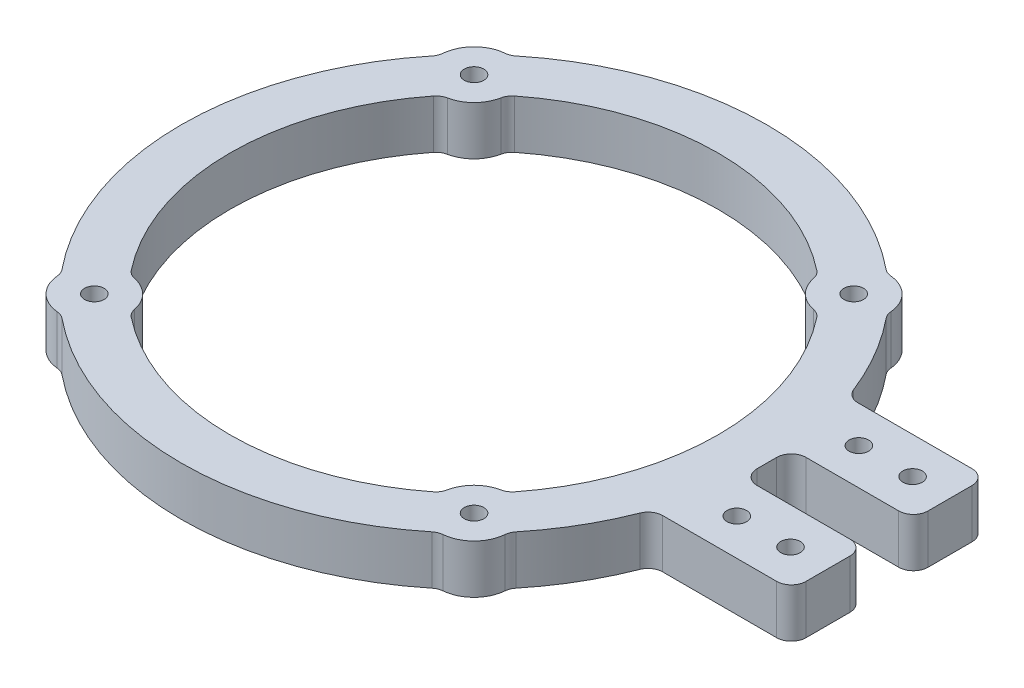
SolidWorks part; units mm, degrees
material "6063-T83"
ref_plane "Front Plane" through (0, 0, 0) normal (0, 0, 1) x (1, 0, 0)
ref_plane "Top Plane" through (0, 0, 0) normal (0, 1, 0) x (1, 0, 0)
ref_plane "Right Plane" through (0, 0, 0) normal (1, 0, 0) x (0, 0, -1)
sketch "Sketch1" plane through (0, 0, 0) normal (0, 1, 0) x (1, 0, 0)
  line L0 (0, -50) -> (0, -60) construction
  line L1 (0, 0) -> (0, -50) construction
  line L2 (56.5685, -20) -> (85, -20)
  line L3 (85, -20) -> (85, -5)
  line L4 (85, -5) -> (60, -5)
  line L5 (60, -5) -> (60, 5)
  line L6 (60, 5) -> (85, 5)
  line L7 (85, 5) -> (85, 20)
  line L8 (85, 20) -> (56.5685, 20)
  circle A0 centre (0, 0) radius 50
  circle A1 centre (0, 0) radius 60 construction
  arc A2 (56.5685, 20) -> (56.5685, -20) centre (0, 0) ccw
  dimension "D1" = 100
  dimension "D2" = 10
  dimension "D3" = 10
  dimension "D4" = 15
  dimension "D6" = 25
extrude "Boss-Extrude1" add sketch "Sketch1" along normal blind 10
sketch "Sketch3" plane through (0, 10, 0) normal (0, 1, 0) x (1, 0, 0)
  line L0 (38.8909, 38.8909) -> (38.8909, -38.8909) construction
  line L1 (60, -5) -> (60, 5) construction
  circle A0 centre (0, 0) radius 55 construction
  circle A1 centre (38.8909, -38.8909) radius 7
  circle A2 centre (-38.8909, -38.8909) radius 7
  circle A3 centre (-38.8909, 38.8909) radius 7
  circle A4 centre (38.8909, 38.8909) radius 7
  point P14 (0, 0)
  dimension "D1" = 110
  dimension "D2" = 14
  dimension "D3" = 4
extrude "Boss-Extrude2" add sketch "Sketch3" against normal up to surface (10 mm away) up to face at (57.0711, 0, 0)
sketch "Sketch4" plane through (0, 10, 0) normal (0, 1, 0) x (1, 0, 0)
  circle A0 centre (38.8909, -38.8909) radius 2
  circle A1 centre (-38.8909, -38.8909) radius 2
  circle A2 centre (-38.8909, 38.8909) radius 2
  circle A3 centre (38.8909, 38.8909) radius 2
  point P12 (0, 0)
  dimension "D1" = 4
  dimension "D2" = 4
extrude "Cut-Extrude1" cut sketch "Sketch4" against normal blind 10
fillet "Fillet1" radius 3 24 edges at (85, 5, -20) (85, 5, -5) (85, 5, 5) (85, 5, 20) (38.5003, 5, 31.9018) (31.9018, 5, 38.5003) (38.5003, 5, -31.9018) (31.9018, 5, -38.5003) (-38.5003, 5, -31.9018) (-31.9018, 5, -38.5003) (-45.887, 5, -38.6573) (-38.6573, 5, -45.887) (38.6573, 5, -45.887) (45.887, 5, -38.6573) (-31.9018, 5, 38.5003) (-38.5003, 5, 31.9018) (-45.887, 5, 38.6573) (-38.6573, 5, 45.887) (38.6573, 5, 45.887) (45.887, 5, 38.6573) (56.5685, 5, 20) (56.5685, 5, -20) (60, 5, 5) (60, 5, -5)
sketch "Sketch5" plane through (0, 10, 0) normal (0, 1, 0) x (1, 0, 0)
  line L0 (58.6515, 20) -> (85, 5) construction
  line L1 (85, 20) -> (58.6515, 5) construction
  line L2 (58.6515, 5) -> (85, 5) construction
  line L3 (58.6515, 20) -> (58.6515, 5) construction
  line L4 (66.3258, 12.5) -> (77.3258, 12.5) construction
  line L5 (58.6515, 20) -> (85, 20) construction
  line L6 (85, 20) -> (85, 5) construction
  line L7 (63, 5) -> (82, 5) construction
  line L8 (85, 8) -> (85, 17) construction
  line L9 (58.6515, -5) -> (85, -20) construction
  line L10 (85, -5) -> (58.6515, -20) construction
  line L11 (58.6515, -20) -> (85, -20) construction
  line L12 (58.6515, -5) -> (58.6515, -20) construction
  line L13 (66.3258, -12.5) -> (77.3258, -12.5) construction
  line L14 (58.6515, -5) -> (85, -5) construction
  line L15 (85, -5) -> (85, -20) construction
  line L16 (82, -5) -> (63, -5) construction
  line L17 (58.6515, -20) -> (82, -20) construction
  circle A0 centre (66.3258, 12.5) radius 2
  circle A1 centre (77.3258, 12.5) radius 2
  circle A2 centre (66.3258, -12.5) radius 2
  circle A3 centre (77.3258, -12.5) radius 2
  point P11 (71.8258, 12.5)
  point P21 (71.8258, -12.5)
  point P27 (66.8258, -12.5)
  dimension "D2" = 4
  dimension "D3" = 4
  dimension "D5" = 4
  dimension "D6" = 4
  dimension "D1" = 11
  dimension "D4" = 11
extrude "Cut-Extrude2" cut sketch "Sketch5" against normal blind 10
